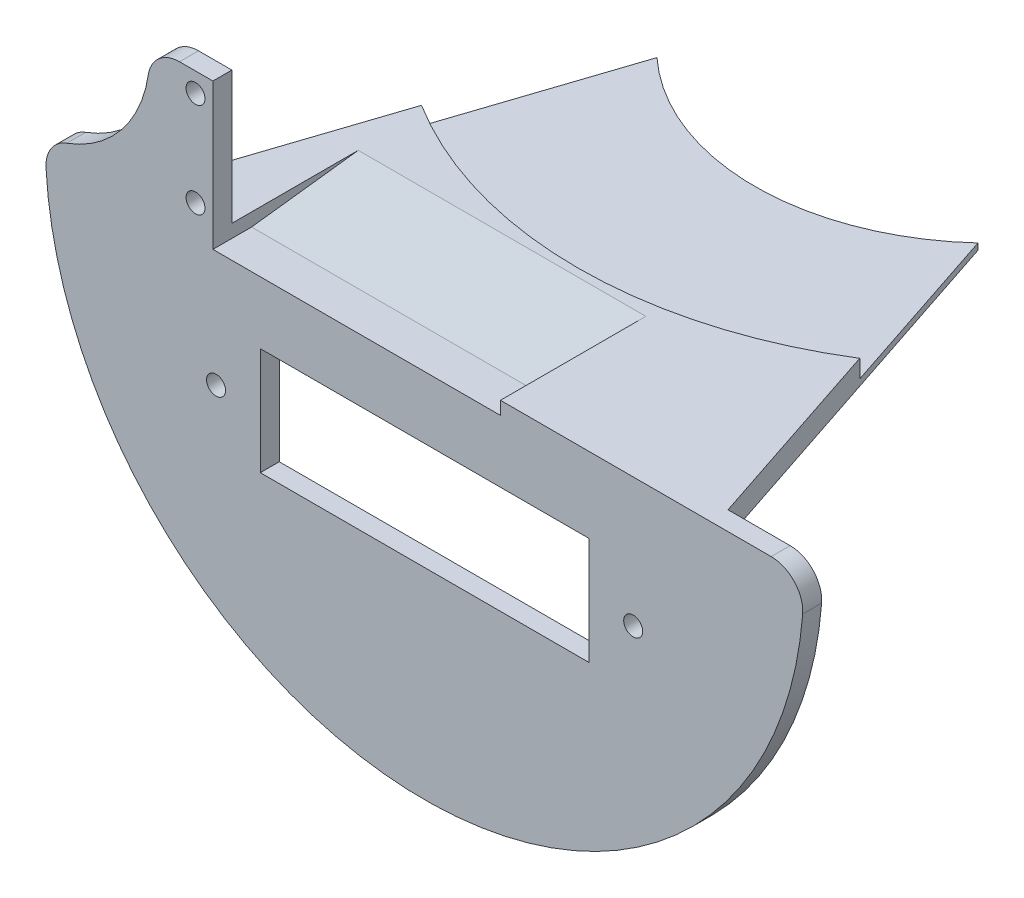
SolidWorks part; units mm, degrees
ref_plane "Front Plane" through (0, 0, 0) normal (0, 0, 1) x (1, 0, 0)
ref_plane "Top Plane" through (0, 0, 0) normal (0, 1, 0) x (1, 0, 0)
ref_plane "Right Plane" through (0, 0, 0) normal (1, 0, 0) x (0, 0, -1)
sketch "Sketch1" plane through (0, 0, 0) normal (0, 0, 1) x (1, 0, 0)
  line L0 (-55.919, 56.6727) -> (12, 56.6727)
  line L2 (-33.5, 35.6727) -> (12, 35.6727)
  line L3 (-26, 6.75) -> (26, 6.75)
  line L4 (-26, 6.75) -> (-26, 23.75)
  line L5 (-26, 23.75) -> (26, 23.75)
  line L6 (26, 6.75) -> (26, 23.75)
  line L7 (-33.5, 35.6727) -> (-33.5, 56.6727)
  line L8 (-33.5, 56.6727) -> (12, 56.6727)
  line L9 (12, 35.6727) -> (12, 56.6727)
  line L10 (12, 35.6727) -> (59.9953, 35.6727)
  line L11 (-43.5, 56.6727) -> (-43.5, 35.6727)
  line L12 (-43.5, 35.6727) -> (-59.9953, 35.6727)
  line L14 (12, 33.6) -> (12, 58.6) construction
  line L15 (-33.5, 58.6) -> (-33.5, 33.6) construction
  arc A0 (-59.988, 33.7227) -> (59.988, 33.7227) centre (0, 34.9227) ccw
  arc A1 (-59.988, 33.7227) -> (-55.919, 56.6727) centre (0, 34.9227) cw
  circle A2 centre (-33, 15.25) radius 1.5
  circle A3 centre (33, 15.25) radius 1.5
  circle A4 centre (-36.25, 53.6) radius 1.5
  circle A5 centre (-36.25, 38.6) radius 1.5
  circle A6 centre (-36.25, 53.6) radius 1.5 construction
  circle A7 centre (-36.25, 38.6) radius 1.5 construction
  arc A8 (59.9953, 35.6727) -> (59.988, 33.7227) centre (0, 34.9227) cw
  point P18 (26, 15.25)
  point P19 (-26, 15.25)
  dimension "D1" = 120
  dimension "D2" = 3
  dimension "D3" = 3
  dimension "D4" = 21
  dimension "D8" = 10
  dimension "D10" = 11.1727
extrude "Boss-Extrude1" add sketch "Sketch1" along normal blind 3 contours A8 L0 L9 L2 L7 A1 A0 A5 A4 A3 A2 L6 L3 L4 L5 region at (-38.5, 55.2207, 0)
sketch "Sketch4" plane through (0, 31.85, 0) normal (0, 1, 0) x (1, 0, 0)
  line L0 (-25.4, 59.1621) -> (-44.991, 0)
  line L2 (-25.4, 41.75) -> (-25.4, 101.25) construction
  line L3 (25.4, 59.1621) -> (45.009, 0)
  line L4 (25.4, 101.25) -> (25.4, 41.75) construction
  line L6 (45.009, 0) -> (-44.991, 0)
  circle A0 centre (0, 86.75) radius 37.5 construction
  arc A1 (25.4, 59.1621) -> (-25.4, 59.1621) centre (0, 86.75) cw
  circle A2 centre (0, 86.75) radius 6.7945 construction
  dimension "D1" = 90
extrude "Boss-Extrude2" add sketch "Sketch4" along normal up to surface (1 mm away)
sketch "Sketch5" plane through (0, 32.85, 0) normal (0, 1, 0) x (1, 0, 0)
  line L0 (-44.991, 0) -> (-25.4, 59.1621) construction
  line L1 (25.4, 59.1621) -> (45.009, 0) construction
  line L2 (-34.6672, 31.1763) -> (-44.991, 0)
  line L3 (-44.991, 0) -> (-44.991, -3)
  line L4 (-44.991, -3) -> (45.009, -3)
  line L5 (45.009, -3) -> (45.009, 0)
  line L6 (45.009, 0) -> (34.6743, 31.1807)
  arc A0 (-34.6672, 31.1763) -> (34.6743, 31.1807) centre (0, 86.75) ccw
  dimension "D1" = 65.5
  dimension "D2" = 90
extrude "Boss-Extrude3" add sketch "Sketch5" along normal up to surface (2.8227 mm away) up to face at (13.2477, 35.6727, 1.5)
fillet "Fillet1" radius 20 1 edges at (-43.5, 35.6727, 1.5)
fillet "Fillet3" radius 5 3 edges at (59.9953, 35.6727, 1.5) (-43.5, 56.6727, 1.5) (-59.9953, 35.6727, 1.5)
sketch "Sketch6" plane through (0, 0, 3) normal (0, 0, 1) x (1, 0, 0)
  line L1 (-33.5, 35.6727) -> (12, 35.6727)
  line L2 (-33.5, 35.6727) -> (-33.5, 33.6)
  line L3 (-33.5, 33.6) -> (12, 33.6)
  line L4 (12, 35.6727) -> (12, 33.6)
extrude "Cut-Extrude1" cut sketch "Sketch6" against normal blind 3
chamfer "Chamfer2" distance 20 angle 7 1 edges at (-10.75, 35.6727, 0) first distance on face at (11.133, 35.6727, -5.1587)
